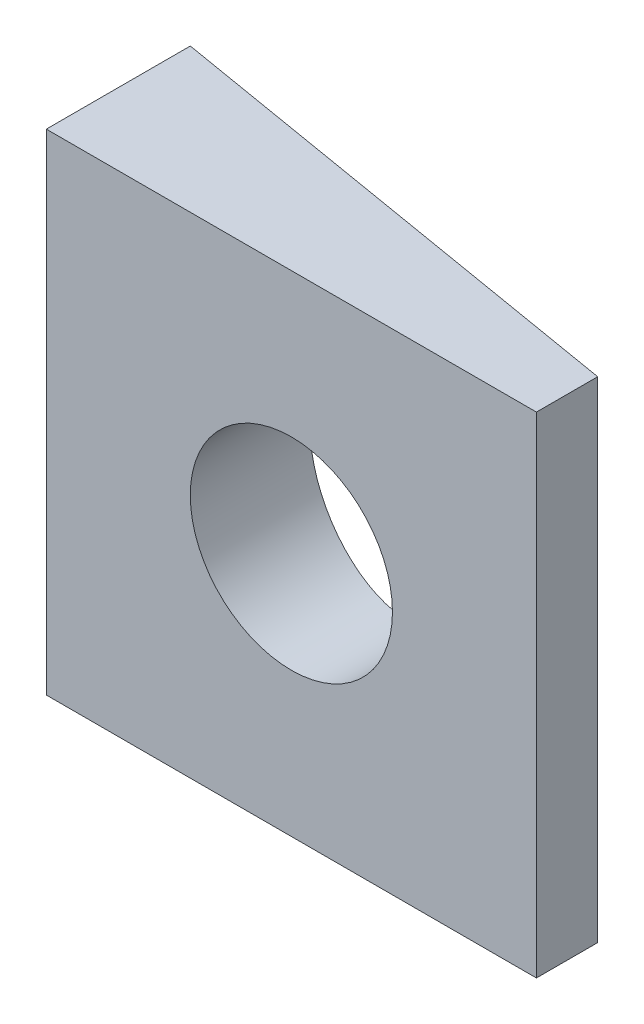
SolidWorks part; units mm, degrees
ref_plane "Front" through (0, 0, 0) normal (0, 0, 1) x (1, 0, 0)
ref_plane "Top" through (0, 0, 0) normal (0, 1, 0) x (1, 0, 0)
ref_plane "Right" through (0, 0, 0) normal (1, 0, 0) x (0, 0, -1)
sketch "Sketch1" plane through (0, 0, 0) normal (0, 0, 1) x (1, 0, 0)
  line L1 (8, 8) -> (-8, 8)
  line L2 (-8, 8) -> (-8, -8)
  line L3 (-8, -8) -> (8, -8)
  line L4 (8, -8) -> (8, 8)
  circle A0 centre (0, 0) radius 8 construction
  circle A1 centre (0, 0) radius 3.3
  dimension "d" = 6.6
  dimension "B" = 16
extrude "Base-Extrude" add sketch "Sketch1" against normal blind 4.7
sketch "Sketch2" plane through (0.1934, 8, -4.2576) normal (0, 1, 0) x (-1, 0, 0)
  line L0 (-7.8066, -0.4424) -> (8.1934, -0.4424)
  line L1 (8.1934, -0.4424) -> (-7.8066, 2.2576)
  line L3 (-7.8066, 2.2576) -> (-7.8066, -0.4424)
  dimension "H" = 2
extrude "Cut-Extrude1" cut sketch "Sketch2" against normal through all
